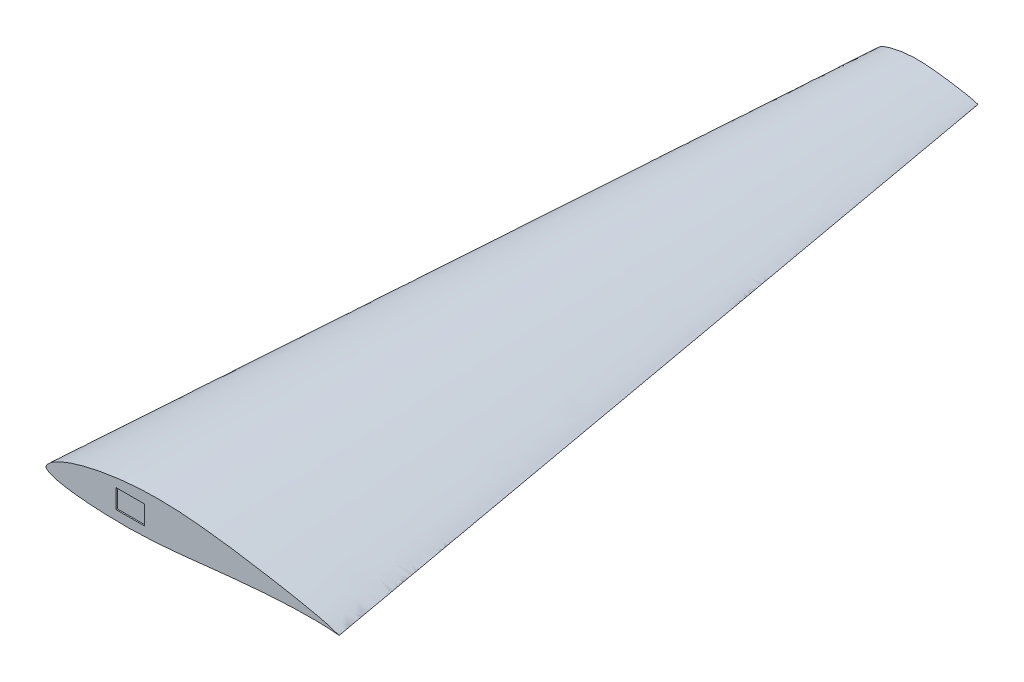
SolidWorks part; units mm, degrees
ref_plane "Front Plane" through (0, 0, 0) normal (0, 0, 1) x (1, 0, 0)
ref_plane "Top Plane" through (0, 0, 0) normal (0, 1, 0) x (1, 0, 0)
ref_plane "Right Plane" through (0, 0, 0) normal (1, 0, 0) x (0, 0, -1)
curve "Curve1"
  spline degree 3 poles (0.9921, 0.0008, 0) (1.0019, -0.0008, 0) (0.9929, 0.0016, 0) (0.9861, 0.0043, 0) (0.9706, 0.0096, 0) (0.9519, 0.0152, 0) (0.9278, 0.021, 0) (0.8992, 0.0273, 0) (0.8662, 0.0341, 0) (0.8293, 0.0413, 0) (0.789, 0.0488, 0) (0.746, 0.0564, 0) (0.7007, 0.0641, 0) (0.6538, 0.0714, 0) (0.6058, 0.0784, 0) (0.5573, 0.0846, 0) (0.5088, 0.0898, 0) (0.4609, 0.0938, 0) (0.4138, 0.0961, 0) (0.3679, 0.0966, 0) (0.3232, 0.0952, 0) (0.2801, 0.092, 0) (0.2388, 0.0874, 0) (0.1997, 0.0815, 0) (0.1631, 0.0746, 0) (0.1296, 0.0669, 0) (0.0993, 0.0585, 0) (0.0726, 0.0496, 0) (0.0499, 0.0404, 0) (0.0312, 0.031, 0) (0.0168, 0.0217, 0) (0.0085, 0.0145, 0) (0.0039, 0.009, 0) (0.0018, 0.0058, 0) (0.0004, 0.0024, 0) (0, 0.0003, 0) (0, -0.0012, 0) (0.0006, -0.0026, 0) (0.002, -0.0043, 0) (0.0049, -0.007, 0) (0.0107, -0.0108, 0) (0.0215, -0.0156, 0) (0.0378, -0.0206, 0) (0.0598, -0.0253, 0) (0.0864, -0.0294, 0) (0.1174, -0.033, 0) (0.1523, -0.036, 0) (0.1908, -0.0383, 0) (0.2323, -0.0397, 0) (0.2764, -0.0402, 0) (0.3228, -0.0395, 0) (0.3711, -0.0373, 0) (0.4212, -0.0335, 0) (0.4729, -0.0284, 0) (0.526, -0.0227, 0) (0.5798, -0.0169, 0) (0.6336, -0.0114, 0) (0.6866, -0.0064, 0) (0.7378, -0.0023, 0) (0.7866, 0.0009, 0) (0.832, 0.0031, 0) (0.8733, 0.0042, 0) (0.9096, 0.0045, 0) (0.9406, 0.0038, 0) (0.9645, 0.0029, 0) (0.984, 0.0013, 0) (0.9921, 0.0008, 0) (1.0019, -0.0008, 0) (0.9929, 0.0016, 0) knots -0.016161 -0.007282 -0.001839 0 0.00178 0.006777 0.014308 0.024046 0.036116 0.050547 0.06713 0.085624 0.105767 0.127282 0.149864 0.17323 0.197069 0.221103 0.245052 0.268663 0.291773 0.314299 0.336178 0.357377 0.377792 0.397225 0.415489 0.432417 0.447849 0.461651 0.473687 0.483898 0.492263 0.498797 0.499955 0.502811 0.504371 0.50536 0.505925 0.506503 0.507535 0.509205 0.512345 0.517665 0.526422 0.537425 0.550643 0.565966 0.583206 0.602155 0.622587 0.644255 0.666998 0.690703 0.715307 0.740824 0.767084 0.793717 0.820331 0.846519 0.871863 0.895937 0.918335 0.938667 0.956573 0.971715 0.983839 0.992718 0.998161 1 1.00178 1.006777 1.014308 periodic
sketch "Sketch1" plane through (0, 0, 0) normal (0, 0, 1) x (1, 0, 0)
  line L0 (1167.2059, -30.8288) -> (-1162.7941, -35.0845) construction
  spline S1 degree 3 poles (1148.7784, -27.977) (1171.7172, -31.8039) (1150.5581, -26.2223) (1134.8254, -19.9356) (1098.6121, -7.5831) (1055.1085, 5.302) (998.7633, 18.7181) (932.1355, 33.1472) (855.1368, 48.7571) (769.1604, 65.315) (675.3297, 82.539) (574.9855, 100.1298) (469.4321, 117.5896) (360.0593, 134.5108) (248.1955, 150.3414) (135.1701, 164.471) (22.251, 176.387) (-89.4773, 185.3614) (-199.1981, 190.448) (-306.2906, 191.3607) (-410.3035, 187.861) (-510.7288, 180.1745) (-606.9241, 169.0794) (-698.0601, 155.2587) (-783.1654, 138.9679) (-861.372, 120.7249) (-931.8769, 100.9237) (-993.9265, 80.0009) (-1046.9152, 58.4337) (-1090.3321, 36.5318) (-1123.8027, 14.8406) (-1143.0848, -2.0984) (-1153.7633, -14.9763) (-1158.687, -22.3942) (-1162.0098, -30.347) (-1162.9632, -35.2319) (-1162.7814, -38.6558) (-1161.4072, -41.8761) (-1158.1965, -46.0146) (-1151.3491, -52.3048) (-1137.7712, -61.0453) (-1112.7076, -72.0855) (-1074.5686, -83.6296) (-1023.3774, -94.5176) (-961.3579, -103.9657) (-889.2059, -112.1487) (-807.7812, -118.8643) (-718.123, -123.9211) (-621.353, -127.1211) (-518.5136, -128.0007) (-410.4966, -125.9274) (-297.9318, -120.4997) (-181.1922, -111.4131) (-60.6773, -99.1751) (62.927, -85.6192) (188.2527, -71.7896) (313.5351, -58.6199) (436.8922, -46.706) (556.3778, -36.7171) (670.0141, -28.9741) (775.8051, -23.5992) (871.9959, -20.7419) (956.4498, -19.9967) (1028.6755, -21.2748) (1084.3745, -23.2358) (1129.9205, -26.8607) (1148.7784, -27.977) (1171.7172, -31.8039) (1150.5581, -26.2223) knots -0.016161 -0.007282 -0.001839 0 0.00178 0.006777 0.014308 0.024046 0.036116 0.050547 0.06713 0.085624 0.105767 0.127282 0.149864 0.17323 0.197069 0.221103 0.245052 0.268663 0.291773 0.314299 0.336178 0.357377 0.377792 0.397225 0.415489 0.432417 0.447849 0.461651 0.473687 0.483898 0.492263 0.498797 0.499955 0.502811 0.504371 0.50536 0.505925 0.506503 0.507535 0.509205 0.512345 0.517665 0.526422 0.537425 0.550643 0.565966 0.583206 0.602155 0.622587 0.644255 0.666998 0.690703 0.715307 0.740824 0.767084 0.793717 0.820331 0.846519 0.871863 0.895937 0.918335 0.938667 0.956573 0.971715 0.983839 0.992718 0.998161 1 1.00178 1.006777 1.014308 only from (1167.2059, -30.8288) to (1167.2059, -30.8288)
  dimension "D1" = 2330
ref_plane "Plane1" through (0, 0, 6200) normal (0, 0, 1) x (1, 0, 0)
ref_plane "Plane3" through (0, -35.0845, 0) normal (0, 1, 0) x (1, 0, 0)
sketch "Sketch4" plane through (0, -35.0845, 0) normal (0, 1, 0) x (1, 0, 0)
  line L1 (1167.2059, 0) -> (-1162.7941, 0) construction
  line L2 (-172.1886, -6200) -> (172.1886, -6200) construction
  line L4 (-1162.7941, 0) -> (-862.7941, -6200)
sketch "Sketch5" plane through (0, 0, 6200) normal (0, 0, 1) x (1, 0, 0)
  line L0 (46.251, -35.2354) -> (-753.7688, -35.3009) construction
  spline S1 degree 3 poles (39.9103, -34.3504) (47.78, -35.5469) (40.5107, -33.741) (35.0952, -31.6671) (22.6402, -27.6181) (7.6874, -23.4229) (-11.663, -19.1093) (-34.5377, -14.4998) (-60.9677, -9.5373) (-90.4749, -4.2947) (-122.6736, 1.1372) (-157.1033, 6.6624) (-193.3153, 12.1171) (-230.8318, 17.3686) (-269.1955, 22.2345) (-307.9483, 26.5125) (-346.6538, 30.0335) (-384.9373, 32.5536) (-422.5145, 33.7529) (-459.1715, 33.5367) (-494.7528, 31.8256) (-529.0855, 28.6992) (-561.9538, 24.4271) (-593.0769, 19.2472) (-622.124, 13.2516) (-648.8002, 6.6219) (-672.8329, -0.5031) (-693.9662, -7.9701) (-711.9952, -15.6131) (-726.7466, -23.3233) (-738.0949, -30.9123) (-744.6106, -36.8049) (-748.2018, -41.2651) (-749.8503, -43.8282) (-750.9483, -46.5664) (-751.2505, -48.243) (-751.1714, -49.4139) (-750.6851, -50.5093) (-749.5659, -51.9099) (-747.1913, -54.0289) (-742.5011, -56.9533) (-733.8685, -60.6082) (-720.7584, -64.3709) (-703.1844, -67.8447) (-681.9116, -70.7722) (-657.1771, -73.2167) (-629.2762, -75.1133) (-598.5656, -76.4015) (-565.4302, -77.0191) (-530.2289, -76.8125) (-493.2702, -75.5698) (-454.7715, -73.1566) (-414.8621, -69.4706) (-373.6761, -64.6873) (-331.4393, -59.4377) (-288.6147, -54.086) (-245.8016, -48.9603) (-203.6413, -44.2739) (-162.7964, -40.2655) (-123.9425, -37.0546) (-87.7619, -34.6929) (-54.8546, -33.2402) (-25.9538, -32.5684) (-1.2281, -32.6493) (17.8446, -33.0456) (33.4506, -34.0614) (39.9103, -34.3504) (47.78, -35.5469) (40.5107, -33.741) knots -0.016161 -0.007282 -0.001839 0 0.00178 0.006777 0.014308 0.024046 0.036116 0.050547 0.06713 0.085624 0.105767 0.127282 0.149864 0.17323 0.197069 0.221103 0.245052 0.268663 0.291773 0.314299 0.336178 0.357377 0.377792 0.397225 0.415489 0.432417 0.447849 0.461651 0.473687 0.483898 0.492263 0.498797 0.499955 0.502811 0.504371 0.50536 0.505925 0.506503 0.507535 0.509205 0.512345 0.517665 0.526422 0.537425 0.550643 0.565966 0.583206 0.602155 0.622587 0.644255 0.666998 0.690703 0.715307 0.740824 0.767084 0.793717 0.820331 0.846519 0.871863 0.895937 0.918335 0.938667 0.956573 0.971715 0.983839 0.992718 0.998161 1 1.00178 1.006777 1.014308 only from (46.2312, -35.2354) to (46.2312, -35.2354)
  dimension "D1" = 800
sketch "Sketch6" plane through (0, 0, 6200) normal (0, 0, 1) x (1, 0, 0)
  line L0 (-753.7688, -35.3009) -> (-751.2083, -48.6103)
  spline S0 degree 3 poles (39.9103, -34.3504) (47.78, -35.5469) (40.5107, -33.741) (35.0952, -31.6671) (22.6402, -27.6181) (7.6874, -23.4229) (-11.663, -19.1093) (-34.5377, -14.4998) (-60.9677, -9.5373) (-90.4749, -4.2947) (-122.6736, 1.1372) (-157.1033, 6.6624) (-193.3153, 12.1171) (-230.8318, 17.3686) (-269.1955, 22.2345) (-307.9483, 26.5125) (-346.6538, 30.0335) (-384.9373, 32.5536) (-422.5145, 33.7529) (-459.1715, 33.5367) (-494.7528, 31.8256) (-529.0855, 28.6992) (-561.9538, 24.4271) (-593.0769, 19.2472) (-622.124, 13.2516) (-648.8002, 6.6219) (-672.8329, -0.5031) (-693.9662, -7.9701) (-711.9952, -15.6131) (-726.7466, -23.3233) (-738.0949, -30.9123) (-744.6106, -36.8049) (-748.2018, -41.2651) (-749.8503, -43.8282) (-750.9483, -46.5664) (-751.2505, -48.243) (-751.1714, -49.4139) (-750.6851, -50.5093) (-749.5659, -51.9099) (-747.1913, -54.0289) (-742.5011, -56.9533) (-733.8685, -60.6082) (-720.7584, -64.3709) (-703.1844, -67.8447) (-681.9116, -70.7722) (-657.1771, -73.2167) (-629.2762, -75.1133) (-598.5656, -76.4015) (-565.4302, -77.0191) (-530.2289, -76.8125) (-493.2702, -75.5698) (-454.7715, -73.1566) (-414.8621, -69.4706) (-373.6761, -64.6873) (-331.4393, -59.4377) (-288.6147, -54.086) (-245.8016, -48.9603) (-203.6413, -44.2739) (-162.7964, -40.2655) (-123.9425, -37.0546) (-87.7619, -34.6929) (-54.8546, -33.2402) (-25.9538, -32.5684) (-1.2281, -32.6493) (17.8446, -33.0456) (33.4506, -34.0614) (39.9103, -34.3504) (47.78, -35.5469) (40.5107, -33.741) knots -0.016161 -0.007282 -0.001839 0 0.00178 0.006777 0.014308 0.024046 0.036116 0.050547 0.06713 0.085624 0.105767 0.127282 0.149864 0.17323 0.197069 0.221103 0.245052 0.268663 0.291773 0.314299 0.336178 0.357377 0.377792 0.397225 0.415489 0.432417 0.447849 0.461651 0.473687 0.483898 0.492263 0.498797 0.499955 0.502811 0.504371 0.50536 0.505925 0.506503 0.507535 0.509205 0.512345 0.517665 0.526422 0.537425 0.550643 0.565966 0.583206 0.602155 0.622587 0.644255 0.666998 0.690703 0.715307 0.740824 0.767084 0.793717 0.820331 0.846519 0.871863 0.895937 0.918335 0.938667 0.956573 0.971715 0.983839 0.992718 0.998161 1 1.00178 1.006777 1.014308 only from (46.2312, -35.2354) to (46.2312, -35.2354) construction
ref_axis "Axis2" through (-751.2083, -48.6103, 6200) along (-0.0662, 0.0022, -0.9978)
loft "Loft5" add profiles "Sketch1", "Sketch5" connector at (-1162.8009, -35.1632, 0) connector at (-751.1274, -47.6465, 6200)
sketch "Sketch7" plane through (0, 0, 0) normal (0, 0, -1) x (-1, 0, 0)
  line L1 (378.6621, 100.8715) -> (605.0337, 100.8715)
  line L2 (378.6621, 100.8715) -> (378.6621, -50.9306)
  line L3 (378.6621, -50.9306) -> (605.0337, -50.9306)
  line L4 (605.0337, 100.8715) -> (605.0337, -50.9306)
extrude "Boss-Extrude1" add sketch "Sketch7" along normal blind 10
mirror "Mirror1" about plane through (0, 0, -10) normal (0, 0, -1) of bodies 110
sketch "Sketch8" plane through (0, 0, 6200) normal (0, 0, 1) x (1, 0, 0)
  line L1 (-1475.8984, 300.6112) -> (1272.5187, 300.6112)
  line L2 (-1475.8984, 300.6112) -> (-1475.8984, -455.7362)
  line L3 (-1475.8984, -455.7362) -> (1272.5187, -455.7362)
  line L4 (1272.5187, 300.6112) -> (1272.5187, -455.7362)
extrude "Cut-Extrude1" cut sketch "Sketch8" against normal blind 6200
sketch "Sketch9" plane through (0, 0, 0) normal (0, 0, 1) x (1, 0, 0)
  line L4 (-378.6621, -50.9306) -> (-378.6621, 100.8715)
  line L5 (-378.6621, 100.8715) -> (-605.0337, 100.8715)
  line L6 (-605.0337, 100.8715) -> (-605.0337, -50.9306)
  line L7 (-605.0337, -50.9306) -> (-378.6621, -50.9306)
  line L8 (-378.6621, -50.9306) -> (-378.6621, 100.8715)
  line L9 (-378.6621, 100.8715) -> (-605.0337, 100.8715)
  line L10 (-605.0337, 100.8715) -> (-605.0337, -50.9306)
  line L11 (-605.0337, -50.9306) -> (-378.6621, -50.9306)
  dimension "D1" = 0
extrude "Cut-Extrude2" cut sketch "Sketch9" against normal blind 30
